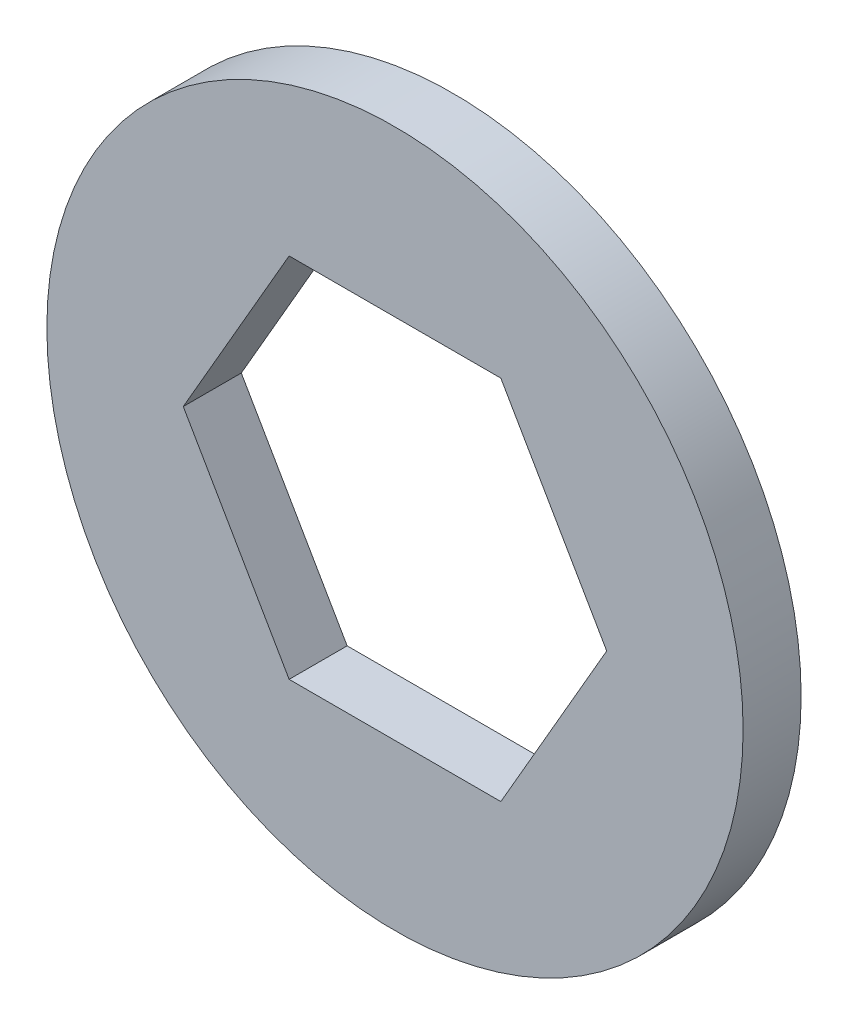
SolidWorks part; units mm, degrees
material "Nylon 101"
ref_plane "Front Plane" through (0, 0, 0) normal (0, 0, 1) x (1, 0, 0)
ref_plane "Top Plane" through (0, 0, 0) normal (0, 1, 0) x (1, 0, 0)
ref_plane "Right Plane" through (0, 0, 0) normal (1, 0, 0) x (0, 0, -1)
sketch "Sketch1" plane through (0, 0, 0) normal (0, 0, 1) x (1, 0, 0)
  line L1 (-5.7926, 0) -> (-2.8963, -5.0165)
  line L2 (-2.8963, -5.0165) -> (2.8963, -5.0165)
  line L3 (2.8963, -5.0165) -> (5.7926, 0)
  line L4 (5.7926, 0) -> (2.8963, 5.0165)
  line L5 (2.8963, 5.0165) -> (-2.8963, 5.0165)
  line L6 (-2.8963, 5.0165) -> (-5.7926, 0)
  circle A0 centre (0, 0) radius 9.525
  circle A2 centre (0, 0) radius 5.0165 construction
  point P3 (0, 0)
  dimension "D1" = 19.05
  dimension "D2" = 10.033
extrude "Boss-Extrude1" add sketch "Sketch1" along normal mid plane 1.5875
equation "\"D1@Boss-Extrude1\"=0.0625in+0.45mm/2"
